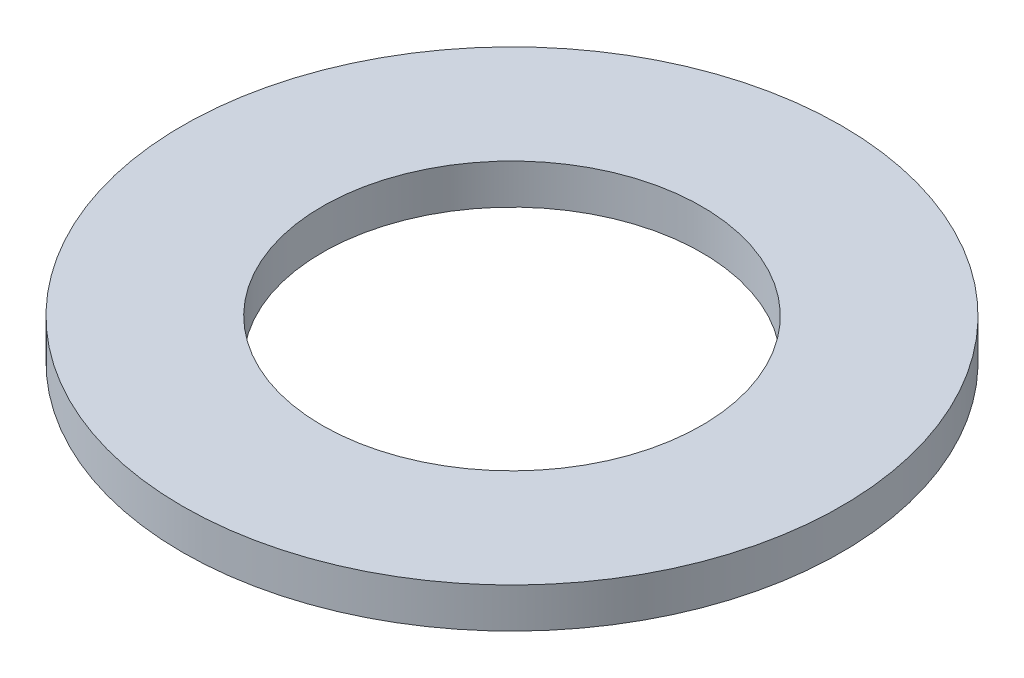
SolidWorks part; units mm, degrees
ref_plane "Front Plane" through (0, 0, 0) normal (0, 0, 1) x (1, 0, 0)
ref_plane "Top Plane" through (0, 0, 0) normal (0, 1, 0) x (1, 0, 0)
ref_plane "Right Plane" through (0, 0, 0) normal (1, 0, 0) x (0, 0, -1)
sketch "Sketch1" plane through (0, 0, 0) normal (0, 1, 0) x (1, 0, 0)
  circle A0 centre (0, 0) radius 82.5
  dimension "FLANGE_OD" = 165
extrude "Boss-Extrude1" add sketch "Sketch1" along normal blind 10
sketch "Sketch2" plane through (0, 0, 0) normal (0, 1, 0) x (1, 0, 0)
  circle A0 centre (0, 0) radius 47.5
  dimension "BORE_D" = 95
extrude "Cut-Extrude1" cut sketch "Sketch2" along normal through all
sketch "Sketch3" plane through (0, 10, 0) normal (0, 1, 0) x (1, 0, 0)
  circle A0 centre (0, 0) radius 33.667 construction
  circle A1 centre (-33.667, 0) radius 1.5685
  dimension "BOLT_D" = 3.1369
  dimension "BOLT_PCD" = 67.334
extrude "Cut-Extrude2" cut sketch "Sketch3" against normal blind 9.598 rebuild error yes
pattern_circular "CirPattern1" count 3 over 360 rebuild error yes
